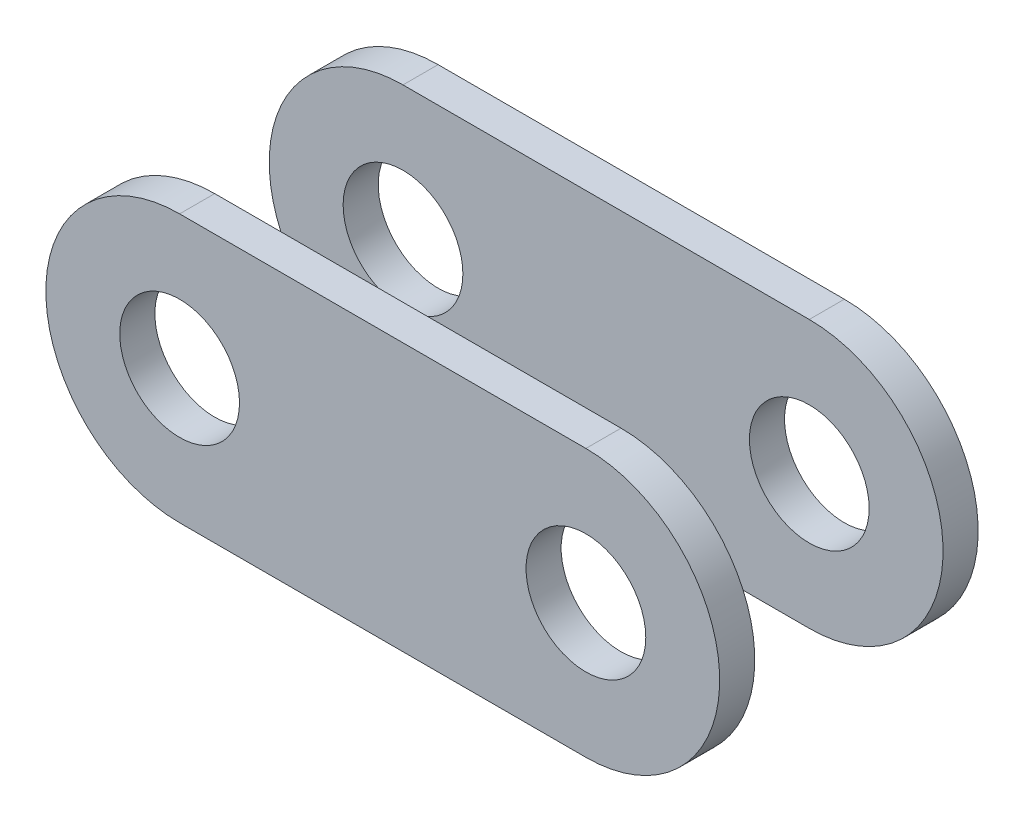
SolidWorks part; units mm, degrees
ref_plane "Front Plane" through (0, 0, 0) normal (0, 0, 1) x (1, 0, 0)
ref_plane "Top Plane" through (0, 0, 0) normal (0, 1, 0) x (1, 0, 0)
ref_plane "Right Plane" through (0, 0, 0) normal (1, 0, 0) x (0, 0, -1)
sketch "Sketch2" plane through (0, 0, 0) normal (0, 0, 1) x (1, 0, 0)
  line L0 (-9.4658, 0) -> (3.031, 0) construction
  line L1 (55, 0) -> (-55, 0) construction
  line L2 (-9.4658, 4.1148) -> (3.031, 4.1148)
  line L3 (-9.4658, -4.1148) -> (3.031, -4.1148)
  arc A0 (-9.4658, 4.1148) -> (-9.4658, -4.1148) centre (-9.4658, 0) ccw
  arc A1 (3.031, -4.1148) -> (3.031, 4.1148) centre (3.031, 0) ccw
  circle A2 centre (-9.4658, 0) radius 1.8415
  circle A3 centre (3.031, 0) radius 1.8415
  point P5 (-3.2174, 0)
  dimension "D1" = 3.683
  dimension "D2" = 3.683
  dimension "D3" = 12.4968
  dimension "D4" = 8.2296
extrude "Boss-Extrude1" add sketch "Sketch2" along normal blind 3.9751 and the other way blind 3.9751
sketch "Sketch3" plane through (0, 4.1148, 0) normal (0, 1, 0) x (1, 0, 0)
  line L0 (-13.5806, 3.9751) -> (-13.5806, -3.9751) construction
  line L1 (-13.5806, 2.8956) -> (7.1458, 2.8956)
  line L2 (-13.5806, 2.8956) -> (-13.5806, -2.8956)
  line L3 (-13.5806, -2.8956) -> (7.1458, -2.8956)
  line L4 (7.1458, 2.8956) -> (7.1458, -2.8956)
  line L5 (7.1458, -3.9751) -> (7.1458, 3.9751) construction
  line L6 (3.031, -3.9751) -> (-9.4658, -3.9751) construction
  dimension "D1" = 5.7912
  dimension "D2" = 1.0795
extrude "Cut-Extrude1" cut sketch "Sketch3" against normal through all
sketch "Sketch6" [suppressed] plane through (0, 4.1148, 0) normal (0, 1, 0) x (1, 0, 0)
  line L0 (-13.5806, 3.9751) -> (-13.5806, -3.9751) construction
  line L1 (-13.5806, 1.6891) -> (7.1458, 1.6891)
  line L2 (-13.5806, 1.6891) -> (-13.5806, -1.6891)
  line L3 (-13.5806, -1.6891) -> (7.1458, -1.6891)
  line L4 (7.1458, 1.6891) -> (7.1458, -1.6891)
  line L5 (7.1458, -3.9751) -> (7.1458, 3.9751) construction
  line L6 (3.031, 3.9751) -> (-9.4658, 3.9751) construction
  line L7 (3.031, -3.9751) -> (-9.4658, -3.9751) construction
  dimension "D1" = 2.286
  dimension "D2" = 2.286
extrude "Cut-Extrude2" [suppressed] cut sketch "Sketch6" against normal through all
sketch "Sketch7" [suppressed] plane through (0, 4.1148, 0) normal (0, 1, 0) x (1, 0, 0)
  line L0 (-13.5806, 3.9751) -> (-13.5806, 1.6891) construction
  line L1 (7.1458, 3.9751) -> (-13.5806, 3.9751)
  line L2 (7.1458, 3.9751) -> (7.1458, 2.8321)
  line L3 (7.1458, 2.8321) -> (-13.5806, 2.8321)
  line L4 (-13.5806, 3.9751) -> (-13.5806, 2.8321)
extrude "Cut-Extrude3" [suppressed] cut sketch "Sketch7" against normal through all
sketch "Sketch8" [suppressed] plane through (0, 4.1148, 0) normal (0, 1, 0) x (1, 0, 0)
  line L0 (-13.5806, -1.6891) -> (-13.5806, -3.9751) construction
  line L1 (7.1458, -3.9751) -> (-13.5806, -3.9751)
  line L2 (7.1458, -3.9751) -> (7.1458, -2.8321)
  line L3 (7.1458, -2.8321) -> (-13.5806, -2.8321)
  line L4 (-13.5806, -3.9751) -> (-13.5806, -2.8321)
  dimension "D1" = 1.143
extrude "Cut-Extrude4" [suppressed] cut sketch "Sketch8" against normal through all
ref_plane "Plane1" through (0, 0, 0) normal (0, 1, 0) x (1, 0, 0)
ref_plane "Plane2" through (0, 0, 0) normal (0, 0, 1) x (1, 0, 0)
equation "\"D1@Sketch2\"= \"D2@Sketch2\""
equation "\"D2@Sketch6\"= \"D1@Sketch6\""
